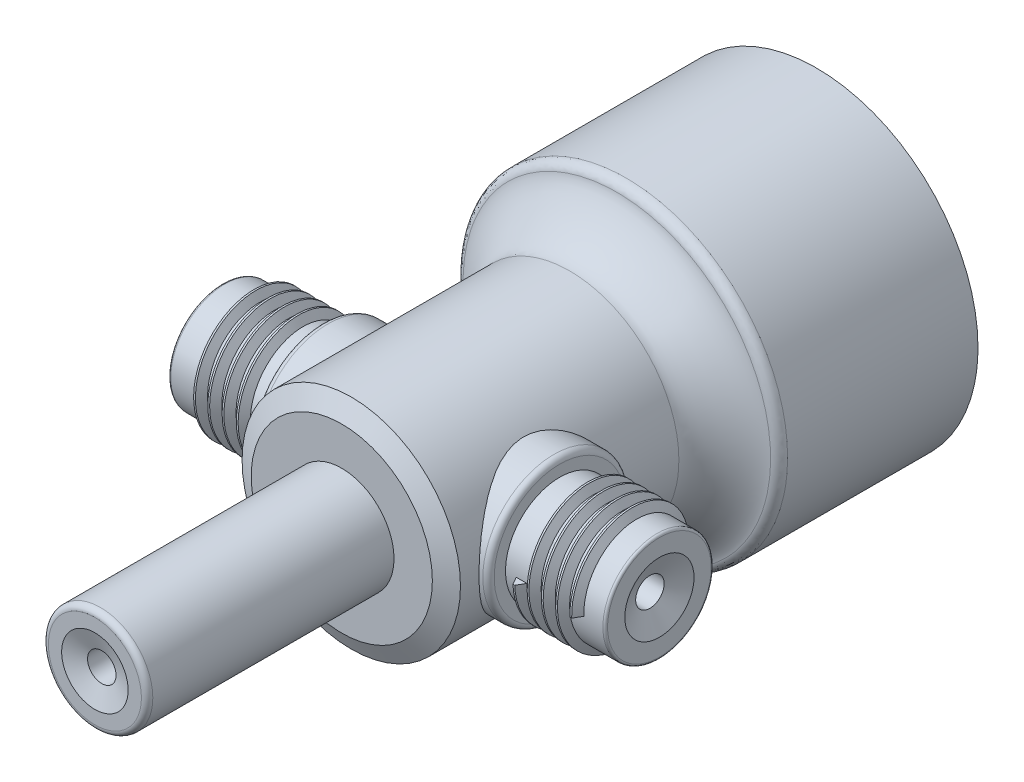
SolidWorks part; units mm, degrees
ref_plane "Спереди" through (0, 0, 0) normal (0, 0, 1) x (1, 0, 0)
ref_plane "Сверху" through (0, 0, 0) normal (0, 1, 0) x (1, 0, 0)
ref_plane "Справа" through (0, 0, 0) normal (1, 0, 0) x (0, 0, -1)
sketch "Эскиз1" plane through (0, 0, 0) normal (0, 0, 1) x (1, 0, 0)
  circle A0 centre (0, 0) radius 17
  dimension "D1" = 34
extrude "Бобышка-Вытянуть1" add sketch "Эскиз1" along normal blind 21
sketch "Эскиз3" plane through (0, 0, 21) normal (0, 0, 1) x (1, 0, 0)
  circle A0 centre (0, 0) radius 11.5
  dimension "D1" = 23
extrude "Бобышка-Вытянуть2" add sketch "Эскиз3" along normal blind 29
sketch "Эскиз8" plane through (0, 0, 50) normal (0, 0, 1) x (1, 0, 0)
  circle A0 centre (0, 0) radius 5.5
  dimension "D1" = 11
extrude "Бобышка-Вытянуть3" add sketch "Эскиз8" along normal blind 26
sketch "Эскиз9" plane through (0, 0, 0) normal (0, 0, -1) x (-1, 0, 0)
  circle A0 centre (0, 0) radius 12.5
  dimension "D1" = 25
extrude "Вырез-Вытянуть1" cut sketch "Эскиз9" against normal blind 15
sketch "Эскиз11" plane through (0, 0, 15) normal (0, 0, -1) x (-1, 0, 0)
  circle A0 centre (0, 0) radius 8
  dimension "D1" = 16
ref_plane "Плоскость5" through (0, 0, 23) normal (0, 0, 1) x (1, 0, 0)
sketch "Эскиз15" plane through (0, 0, 23) normal (0, 0, 1) x (1, 0, 0)
  circle A0 centre (0, 0) radius 11.5
  dimension "D1" = 23
fillet "Скругление30" radius 5 1 edges at (11.5, 0, 21) type face fillet first side face at (11.5, 0, 50) second side face at (11.5, 0, 21) conic radius 10
fillet "Скругление31" radius 1 1 edges at (17, 0, 21)
chamfer "Фаска7" distance 1 angle 62.976 1 edges at (11.5, 0, 50)
sketch "Эскиз16" plane through (0, 0, 0) normal (0, 1, 0) x (1, 0, 0)
  line L0 (17, -20.051) -> (17, -32.051)
  line L1 (17, -32.051) -> (17, -47.051)
  dimension "D1" = 12
  dimension "D2" = 15
sketch "Эскиз18" plane through (0, 0, 0) normal (0, 1, 0) x (1, 0, 0)
  line L0 (17, -32.051) -> (0, -32.051)
sketch "Эскиз19" plane through (0, 0, 0) normal (1, 0, 0) x (0, 0, -1)
  line L0 (-32.051, 0) -> (-34.051, 0)
  circle A0 centre (-39.551, 0) radius 5.5
  dimension "D3" = 11
  dimension "D1" = 2
  dimension "D2" = 5.5
extrude "Вырез-Вытянуть3" cut sketch "Эскиз19" against normal through all both and the other way through all contours A0 region at (0, 0, 39.551)
sketch "Эскиз20" plane through (0, 0, 0) normal (1, 0, 0) x (0, 0, -1)
  line L1 (-32.051, 0) -> (-39.551, 0)
  circle A0 centre (-39.551, 0) radius 5.705
  dimension "D1" = 7.5
sketch "Эскиз21" plane through (0, 0, 0) normal (1, 0, 0) x (0, 0, -1)
  circle A0 centre (-39.551, 0) radius 7.5
  dimension "D1" = 15
extrude "Бобышка-Вытянуть5" add sketch "Эскиз21" along normal blind 12.5 and the other way blind 12.5 separate body contours A0
extrude "Бобышка-Вытянуть6" add sketch "Эскиз20" along normal blind 23 and the other way blind 23 separate body contours A0
fillet "Скругление34" radius 0.6 1 edges at (-12.5, 0, 32.051)
fillet "Скругление35" radius 0.6 1 edges at (12.5, 0, 32.051)
sketch "Эскиз24" plane through (23, 0, 0) normal (1, 0, 0) x (0, 0, -1)
  circle A0 centre (-39.551, 0) radius 1.5
  circle A1 centre (-39.551, 0) radius 5.705 construction
  dimension "D1" = 3
extrude "Вырез-Вытянуть4" cut sketch "Эскиз24" against normal blind 50
sketch "Эскиз25" plane through (-23, 0, 0) normal (-1, 0, 0) x (0, 0, 1)
  circle A0 centre (39.551, 0) radius 3.75
  dimension "D1" = 7.5
sketch "Эскиз26" plane through (23, 0, 0) normal (1, 0, 0) x (0, 0, -1)
  circle A0 centre (-39.551, 0) radius 3.75
  dimension "D1" = 7.5
fillet "Скругление37" radius 0.25 1 edges at (23, 0, 33.846)
fillet "Скругление38" radius 0.25 1 edges at (-23, 0, 33.846)
sketch "Эскиз28" plane through (0, 0, 76) normal (0, 0, 1) x (1, 0, 0)
  circle A0 centre (0, 0) radius 1.5
  dimension "D1" = 3
extrude "Вырез-Вытянуть8" cut sketch "Эскиз28" against normal blind 118
fillet "Скругление39" radius 0.6 1 edges at (5.5, 0, 76)
extrude "Вырез-Вытянуть9" cut sketch "Эскиз11" against normal blind 20.828 contours A0
sketch "Эскиз30" plane through (0, 0, 0) normal (0, 0, -1) x (-1, 0, 0)
  circle A0 centre (0, 0) radius 14
  dimension "D1" = 28
chamfer "Фаска8" distance 2 angle 20 1 edges at (1.5, 0, 76) first distance on face at (4.9, 0, 76)
chamfer "Фаска9" distance 1 angle 65 1 edges at (-23, 0, 38.051) first distance on face at (-1.5, 0, 39.551)
chamfer "Фаска10" distance 1 angle 65 1 edges at (23, 0, 38.051) first distance on face at (23, 0, 38.051)
sketch "Эскиз34" plane through (0, 0, 35.828) normal (0, 0, -1) x (-1, 0, 0)
  circle A0 centre (0, 0) radius 3
  dimension "D1" = 6
extrude "Вырез-Вытянуть11" cut sketch "Эскиз34" against normal blind 9
ref_plane "Плоскость4" through (8.5, 0, 0) normal (1, 0, 0) x (0, 0, -1)
sketch "Эскиз36" plane through (8.5, 0, 0) normal (1, 0, 0) x (0, 0, -1)
  circle A0 centre (-39.551, 0) radius 7.5
  dimension "D1" = 15
thread "Резьба1" pitch 1.5 method extrude profile "Профиль резьбы1" start angle 0, offset 2, length 6, pitch 1.5, diameter 11.41
ref_plane "Плоскость6" through (20.75, 0, 45.256) normal (0, -1, 0) x (0, 0, 1)
sketch "Профиль резьбы1" plane through (20.75, 0, 45.256) normal (0, -1, 0) x (0, 0, 1)
  line L0 (0, 0) -> (0, 1.5) construction
  line L1 (0, 0) -> (0.8119, 0.4687)
  line L2 (0.8119, 0.4687) -> (0.8119, 0.6562)
  line L3 (0.8119, 0.6562) -> (0, 1.125)
  line L4 (0.8119, 0.5625) -> (0, 0.5625) construction
  line L11 (0, 0) -> (0, 1.125)
  point P2 (0, 0)
  dimension "Pitch" = 1.5
  dimension "Profile_Angle" = 60
  dimension "Profile_Land" = 0.1875
  dimension "Profile_Height" = 0.8119
sketch "Эскиз49" plane through (0, 0, 0) normal (0, 1, 0) x (1, 0, 0)
  line L4 (14.0938, -46.0679) -> (14.2813, -46.0679)
  line L5 (14.2813, -46.0679) -> (14.75, -45.256)
  line L6 (14.75, -45.256) -> (13.625, -45.256)
  line L7 (13.625, -45.256) -> (14.0938, -46.0679)
  line L8 (14.0938, -46.0679) -> (14.2813, -46.0679)
  line L9 (14.2813, -46.0679) -> (14.75, -45.256)
  line L10 (14.75, -45.256) -> (13.625, -45.256)
  line L11 (13.625, -45.256) -> (14.0938, -46.0679)
  dimension "D1" = 0
thread "Резьба3" pitch 1.5 method extrude profile "Профиль резьбы4" start angle 0, offset 2, length 6, pitch 1.5, diameter 11.41
ref_plane "Плоскость9" through (-20.75, 0, 33.846) normal (0, -1, 0) x (0, 0, -1)
sketch "Профиль резьбы4" plane through (-20.75, 0, 33.846) normal (0, -1, 0) x (0, 0, -1)
  line L0 (0, 0) -> (0, 1.5) construction
  line L1 (0, 0) -> (0.8119, 0.4687)
  line L2 (0.8119, 0.4687) -> (0.8119, 0.6562)
  line L3 (0.8119, 0.6562) -> (0, 1.125)
  line L4 (0.8119, 0.5625) -> (0, 0.5625) construction
  line L11 (0, 0) -> (0, 1.125)
  point P2 (0, 0)
  dimension "Pitch" = 1.5
  dimension "Profile_Angle" = 60
  dimension "Profile_Land" = 0.1875
  dimension "Profile_Height" = 0.8119
thread "Резьба4" pitch 1.75 method cut profile "Профиль резьбы6" start angle 0, offset 0, length 9, pitch 1.75, diameter 25
ref_plane "Плоскость11" through (12.5, 0, 0) normal (0, -1, 0) x (1, 0, 0)
sketch "Профиль резьбы6" plane through (12.5, 0, 0) normal (0, -1, 0) x (1, 0, 0)
  line L0 (0, 0) -> (0, 1.75) construction
  line L1 (0, 0) -> (0.9472, 0.5469)
  line L2 (0.9472, 0.5469) -> (0.9472, 0.7656)
  line L3 (0.9472, 0.7656) -> (0, 1.3125)
  line L4 (0.9472, 0.6562) -> (0, 0.6562) construction
  line L11 (0, 0) -> (0, 1.3125)
  point P2 (0, 0)
  dimension "Pitch" = 1.75
  dimension "Profile_Angle" = 60
  dimension "Profile_Land" = 0.2188
  dimension "Profile_Height" = 0.9472
